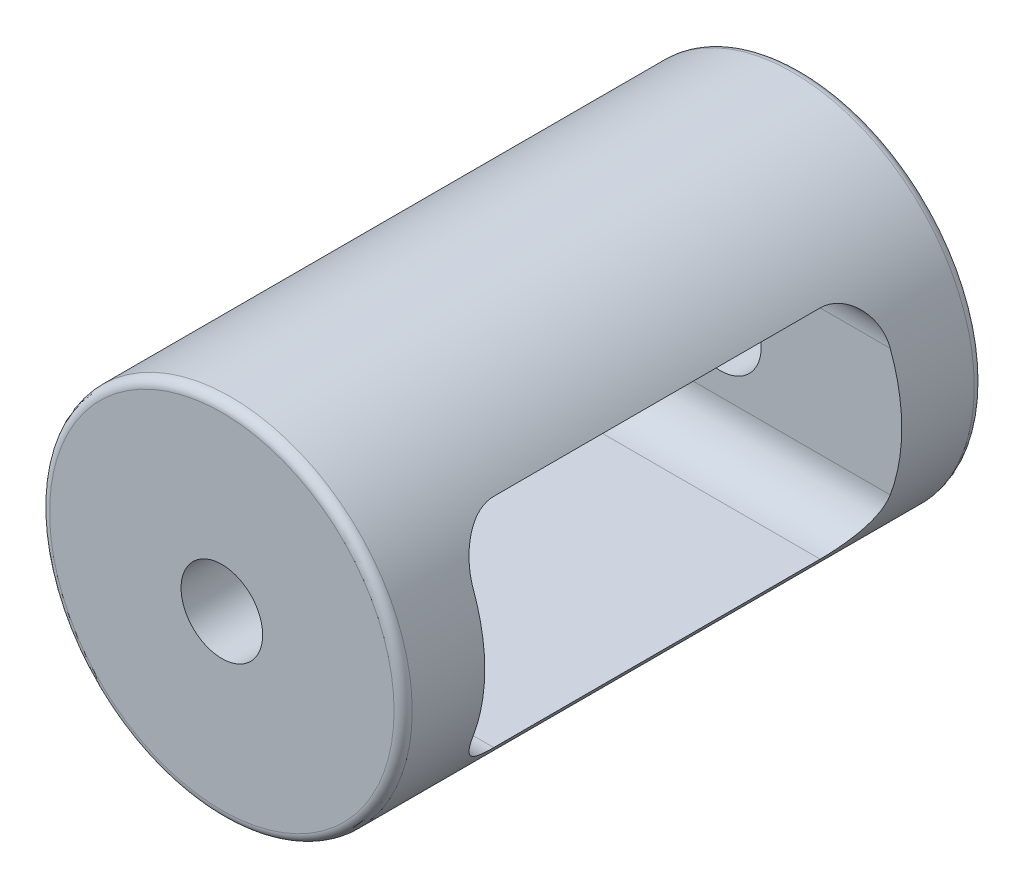
SolidWorks part; units mm, degrees
ref_plane "Front Plane" through (0, 0, 0) normal (0, 0, 1) x (1, 0, 0)
ref_plane "Top Plane" through (0, 0, 0) normal (0, 1, 0) x (1, 0, 0)
ref_plane "Right Plane" through (0, 0, 0) normal (1, 0, 0) x (0, 0, -1)
sketch "Sketch1" plane through (0, 0, 0) normal (0, 0, 1) x (1, 0, 0)
  circle A0 centre (0, 0) radius 10
  circle A1 centre (0, 0) radius 2.25
  dimension "D1" = 20
  dimension "D2" = 4.5
extrude "Boss-Extrude1" add sketch "Sketch1" along normal blind 16 and the other way blind 16
sketch "Sketch2" plane through (0, 0, 0) normal (1, 0, 0) x (0, 0, -1)
  line L0 (-11.5, 6) -> (11.5, -6) construction
  line L1 (-11.5, 6) -> (11.5, 6)
  line L2 (-11.5, 6) -> (-11.5, -6)
  line L3 (-11.5, -6) -> (11.5, -6)
  line L4 (11.5, 6) -> (11.5, -6)
  line L5 (16, -2.25) -> (16, 2.25) construction
  dimension "D1" = 12
  dimension "D2" = 4.5
extrude "Cut-Extrude1" cut sketch "Sketch2" against normal through all both and the other way through all
fillet "Fillet1" radius 0.5 2 edges at (10, 0, -16) (10, 0, 16)
fillet "Fillet2" radius 2.5 4 edges at (0, 6, 11.5) (0, -6, 11.5) (0, -6, -11.5) (0, 6, -11.5)
